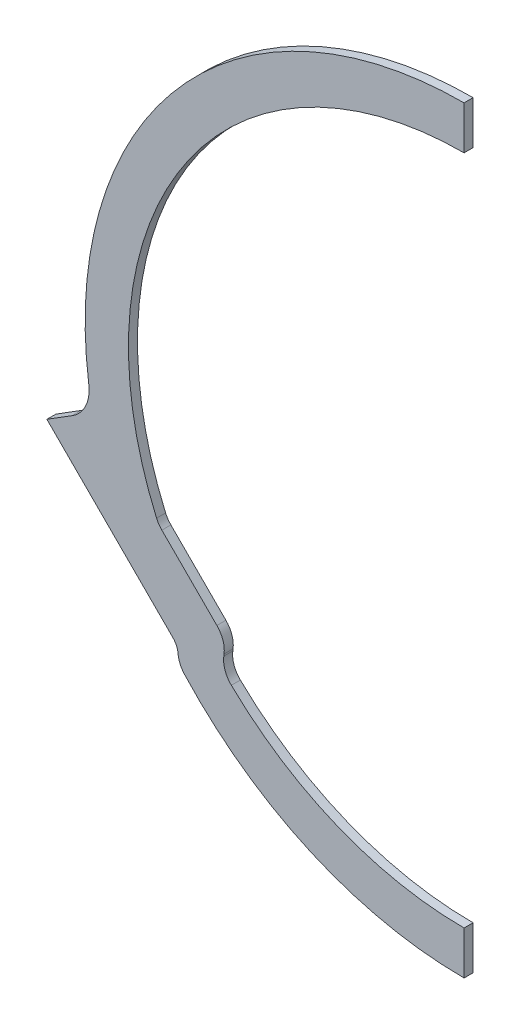
SolidWorks part; units mm, degrees
material "Balsa"
ref_plane "Front Plane" through (0, 0, 0) normal (0, 0, 1) x (1, 0, 0)
ref_plane "Top Plane" through (0, 0, 0) normal (0, 1, 0) x (1, 0, 0)
ref_plane "Right Plane" through (0, 0, 0) normal (1, 0, 0) x (0, 0, -1)
sketch "Sketch1" plane through (0, 0, 0) normal (0, 0, 1) x (1, 0, 0)
  line L0 (0, -110.0909) -> (0, -70.6286) construction
  line L2 (0, 0) -> (0, 631.6453) construction
  line L3 (-120.188, -34.2725) -> (-99.9824, -54.478)
  line L4 (0, 0) -> (-284.8905, 0) construction
  line L5 (-99.9824, -54.478) -> (-101.1426, -63.4095)
  line L8 (-99.9824, -54.478) -> (-57.7675, -96.693) construction
  line L9 (-99.9824, -54.478) -> (0, 0) construction
  line L10 (-101.1426, -63.4095) -> (0, 0) construction
  arc A0 (-57.7675, -96.693) -> (-120.188, -34.2725) centre (0, 23.495) ccw
  arc A2 (-120.188, -34.2725) -> (-57.7675, -96.693) centre (0, 23.495) ccw construction
  arc A3 (-101.1426, -63.4095) -> (-57.7675, -96.693) centre (0, 23.495) ccw
  point P0 (0, 0)
  point P2 (0, 156.7839)
  point P3 (0, -109.8059)
  point P15 (-99.9824, -54.478)
  dimension "D1" = 266.5898
  dimension "D2" = 266.7
  dimension "D3" = 23.495
  dimension "D5" = 109.22
  dimension "D6" = 45
  dimension "D7" = 28.575
  dimension "D4" = 3.5
extrude "Boss-Extrude1" add sketch "Sketch1" along normal mid plane 3.175
sketch "Sketch2" plane through (0, 0, 1.5875) normal (0, 0, 1) x (1, 0, 0)
  line L4 (-83.9033, -49.0045) -> (-85.1218, -58.3845)
  line L5 (-107.5191, -25.3887) -> (-83.9033, -49.0045)
  line L6 (-83.9033, -49.0045) -> (-85.1218, -58.3845)
  line L7 (-107.5191, -25.3887) -> (-83.9033, -49.0045)
  arc A2 (-85.1218, -58.3845) -> (-107.5191, -25.3887) centre (0, 23.495) ccw
  arc A3 (-85.1218, -58.3845) -> (-107.5191, -25.3887) centre (0, 23.495) ccw
  dimension "D1" = 15.24
extrude "Cut-Extrude1" cut sketch "Sketch2" against normal up to surface (3.175 mm away) up to face at (-33.0092, -2.288, -1.5875)
fillet "Fillet1" radius 8.89 6 edges at (-107.5191, -25.3887, 0) (-120.188, -34.2725, 0) (-101.1426, -63.4095, 0) (-99.9824, -54.478, 0) (-83.9033, -49.0045, 0) (-85.1218, -58.3845, 0)
sketch "Sketch3" plane through (0, 0, 0) normal (1, 0, 0) x (0, 0, -1)
  line L1 (-107.0531, 227.715) -> (127.3903, 227.715)
  line L2 (-107.0531, 227.715) -> (-107.0531, -194.8481)
  line L3 (-107.0531, -194.8481) -> (127.3903, -194.8481)
  line L4 (127.3903, 227.715) -> (127.3903, -194.8481)
extrude "Cut-Extrude2" cut sketch "Sketch3" along normal through all
sketch "Sketch5" plane through (0, 0, 0) normal (0, 0, 1) x (1, 0, 0)
  line L0 (-146.8166, -13.0034) -> (-125.2935, 0.4458)
  line L1 (-146.8166, -13.0034) -> (-100.6004, -59.2359)
  line L2 (0, 0) -> (-240.0313, 0) construction
  line L3 (-100.6004, -59.2359) -> (-91.9691, -50.6076)
  line L4 (-91.9691, -50.6076) -> (-125.2935, 0.4458)
  ellipse E0 centre (0.6289, 30.2513) end of major axis (130.0331, 30.2513) minor radius 129.3587 (-127.7603, 14.0811) -> (-84.313, -67.3377) ccw construction
  dimension "D1" = 45.01
  dimension "D2" = 113.0265
  dimension "D3" = 116.7447
  dimension "D4" = 32
  dimension "D5" = 65.3711
extrude "Boss-Extrude2" add sketch "Sketch5" along normal mid plane 3.175
fillet "Fillet2" radius 6.35 1 edges at (-100.6004, -59.2359, 0)
fillet "Fillet3" radius 12.7 1 edges at (-130.7045, -2.9354, 0)
